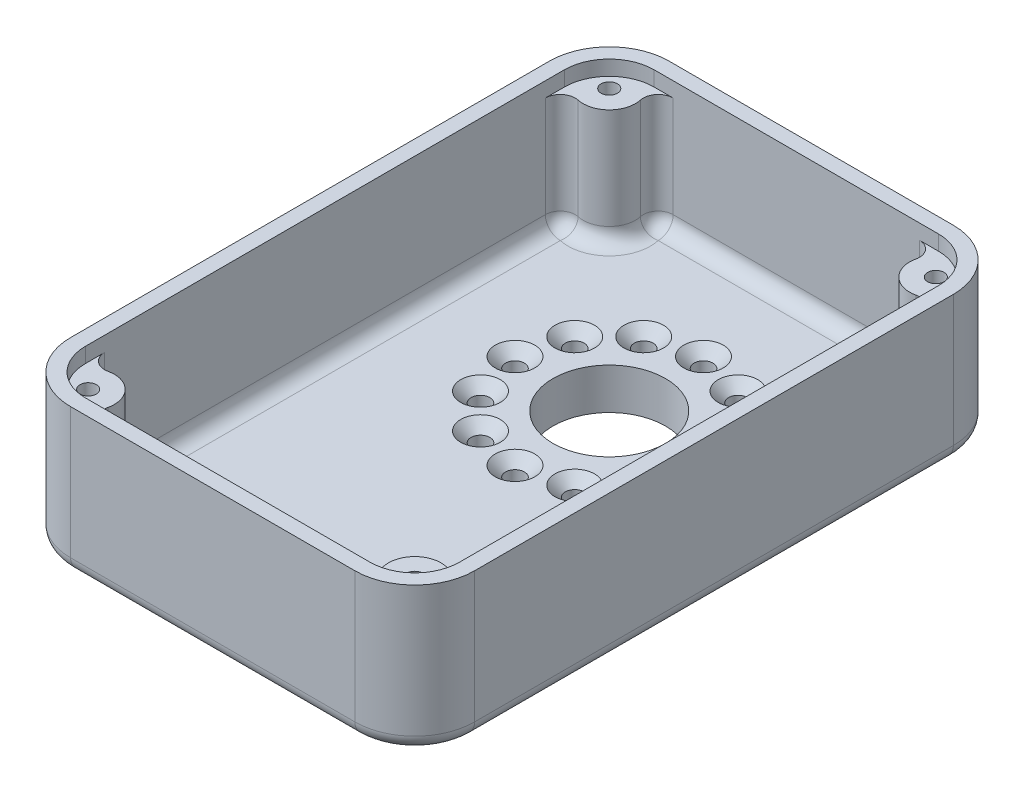
SolidWorks part; units mm, degrees
ref_plane "Front Plane" through (0, 0, 0) normal (0, 0, 1) x (1, 0, 0)
ref_plane "Top Plane" through (0, 0, 0) normal (0, 1, 0) x (1, 0, 0)
ref_plane "Right Plane" through (0, 0, 0) normal (1, 0, 0) x (0, 0, -1)
sketch "Sketch1" plane through (0, 0, 0) normal (0, 0, 1) x (1, 0, 0)
  line L0 (0, 0) -> (0, 10.3527) construction
  line L1 (-9.5504, 0) -> (-20.574, 0)
  line L2 (-20.574, 0) -> (-20.574, -5.08)
  line L3 (-20.574, -5.08) -> (-13.208, -5.08)
  line L4 (-13.208, -5.08) -> (-13.208, -4.445)
  line L5 (-13.208, -4.445) -> (-9.5504, -4.445)
  line L6 (-9.5504, -4.445) -> (-9.5504, 0)
  dimension "D1" = 20.574
  dimension "D2" = 9.5504
  dimension "D3" = 13.208
  dimension "D4" = 5.08
  dimension "D5" = 0.635
revolve "Revolve1" add sketch "Sketch1" angle 360 about L0
sketch "Sketch4" plane through (0, 0, 0) normal (0, 1, 0) x (1, 0, 0)
  line L0 (0, 0) -> (0, -36.4153) construction
  line L1 (-34.29, -16.51) -> (34.29, -16.51) construction
  line L2 (24.13, -67.31) -> (-24.13, -67.31)
  line L3 (34.29, -57.15) -> (34.29, 24.13)
  line L4 (24.13, 34.29) -> (-24.13, 34.29)
  line L5 (-34.29, -57.15) -> (-34.29, 24.13)
  line L6 (34.29, -67.31) -> (-34.29, 34.29) construction
  line L7 (34.29, 34.29) -> (-34.29, -67.31) construction
  line L8 (-24.13, -57.15) -> (0, -33.02) construction
  circle A0 centre (0, 0) radius 20.574 construction
  circle A1 centre (0, 0) radius 9.5504
  circle A2 centre (0, 0) radius 28.2956 construction
  circle A3 centre (0, 0) radius 30.8356 construction
  arc A4 (-34.29, -57.15) -> (-24.13, -67.31) centre (-24.13, -57.15) ccw
  arc A5 (24.13, -67.31) -> (34.29, -57.15) centre (24.13, -57.15) ccw
  arc A6 (34.29, 24.13) -> (24.13, 34.29) centre (24.13, 24.13) ccw
  arc A7 (-24.13, 34.29) -> (-34.29, 24.13) centre (-24.13, 24.13) ccw
  point P3 (0, -16.51)
  dimension "D3" = 34.29
  dimension "D4" = 2.54
  dimension "D5" = 10.16
  dimension "D1" = 68.58
  dimension "D2" = 101.6
  dimension "D6" = 135
extrude "Boss-Extrude1" add sketch "Sketch4" along normal blind 2.54
hole_wizard "CSK for M3 SFHCS1" positions "Sketch3" profile "Sketch2" countersink size "M3" standard "ANSI Metric" end condition through all
sketch "Sketch3" plane through (0, 2.54, 0) normal (0, 1, 0) x (1, 0, 0)
  line L0 (0, 0) -> (0, 1.3105) construction
  line L2 (0, 0) -> (-5.7425, 0) construction
  circle A0 centre (0, 0) radius 16.002 construction
  point P6 (-16.002, 0)
  point P15 (-13.8581, 8.001)
  point P16 (-8.001, 13.8581)
  point P34 (0, 16.002)
  point P35 (8.001, 13.8581)
  point P36 (13.8581, 8.001)
  point P37 (16.002, 0)
  point P38 (13.8581, -8.001)
  point P39 (8.001, -13.8581)
  point P40 (0, -16.002)
  point P41 (-8.001, -13.8581)
  point P42 (-13.8581, -8.001)
  dimension "D1" = 32.004
  dimension "D2" = 12
sketch "Sketch2" plane through (-13.8581, 2.54, 8.001) normal (1, 0, 0) x (0, 0, 1)
  line L0 (0, 0) -> (0, 7.62)
  line L1 (0, 7.62) -> (1.6, 7.62)
  line L2 (1.6, 7.62) -> (1.6, 1.76)
  line L3 (1.6, 1.76) -> (3.36, 0)
  line L5 (3.36, 0) -> (0, 0)
  line L6 (-1.6, 1.76) -> (-3.36, 0) construction
  line L11 (0, -6.35) -> (0, 107.95) construction
  dimension "Thru Hole Dia." = 3.2
  dimension "Thru Hole Depth" = 7.62
  dimension "Near C'Sink Dia." = 6.72
  dimension "Near C'Sink Angle" = 90
sketch "Sketch6" plane through (0, 2.54, 0) normal (0, 1, 0) x (1, 0, 0)
  line L6 (24.13, 34.29) -> (-24.13, 34.29)
  line L7 (-34.29, 24.13) -> (-34.29, -57.15)
  line L8 (-24.13, -67.31) -> (24.13, -67.31)
  line L9 (34.29, -57.15) -> (34.29, 24.13)
  line L10 (24.13, 31.75) -> (-24.13, 31.75)
  line L19 (31.75, -57.15) -> (31.75, 24.13)
  line L20 (-24.13, -64.77) -> (24.13, -64.77)
  line L21 (-31.75, 24.13) -> (-31.75, -57.15)
  line L22 (24.13, 31.75) -> (-24.13, 31.75)
  line L23 (31.75, -57.15) -> (31.75, 24.13)
  line L24 (-24.13, -64.77) -> (24.13, -64.77)
  line L25 (-31.75, 24.13) -> (-31.75, -57.15)
  arc A5 (-24.13, 34.29) -> (-34.29, 24.13) centre (-24.13, 24.13) ccw
  arc A6 (-34.29, -57.15) -> (-24.13, -67.31) centre (-24.13, -57.15) ccw
  arc A14 (24.13, -67.31) -> (34.29, -57.15) centre (24.13, -57.15) ccw
  arc A15 (34.29, 24.13) -> (24.13, 34.29) centre (24.13, 24.13) ccw
  arc A16 (31.75, 24.13) -> (24.13, 31.75) centre (24.13, 24.13) ccw
  arc A17 (-24.13, 31.75) -> (-31.75, 24.13) centre (-24.13, 24.13) ccw
  arc A18 (24.13, -64.77) -> (31.75, -57.15) centre (24.13, -57.15) ccw
  arc A19 (-31.75, -57.15) -> (-24.13, -64.77) centre (-24.13, -57.15) ccw
  arc A20 (31.75, 24.13) -> (24.13, 31.75) centre (24.13, 24.13) ccw
  arc A21 (-24.13, 31.75) -> (-31.75, 24.13) centre (-24.13, 24.13) ccw
  arc A22 (24.13, -64.77) -> (31.75, -57.15) centre (24.13, -57.15) ccw
  arc A23 (-31.75, -57.15) -> (-24.13, -64.77) centre (-24.13, -57.15) ccw
  dimension "D1" = 2.54
  dimension "D2" = 2.54
extrude "Boss-Extrude4" add sketch "Sketch6" along normal blind 22.225
fillet "Fillet1" radius 2.54 8 edges at (-31.3142, 0, 64.3342) (-34.29, 0, 16.51) (-31.3142, 0, -31.3142) (0, 0, -34.29) (31.3142, 0, -31.3142) (34.29, 0, 16.51) (31.3142, 0, 64.3342) (0, 0, 67.31)
sketch "Sketch8" plane through (0, 2.54, 0) normal (0, 1, 0) x (1, 0, 0)
  line L0 (-24.13, -57.15) -> (-46.8517, -79.8717) construction
  line L1 (-34.29, 24.13) -> (-34.29, -57.15) construction
  line L2 (0, -64.77) -> (0, 31.75) construction
  line L3 (-24.13, -64.77) -> (24.13, -64.77) construction
  line L4 (24.13, 31.75) -> (-24.13, 31.75) construction
  line L5 (0, -16.51) -> (-37.3684, -16.51) construction
  circle A0 centre (-27.7221, -60.7421) radius 4.445
  circle A1 centre (-27.7221, -60.7421) radius 1.3891
  circle A3 centre (27.7221, -60.7421) radius 1.3891
  circle A5 centre (27.7221, -60.7421) radius 4.445
  circle A6 centre (27.7221, 27.7221) radius 1.3891
  circle A7 centre (27.7221, 27.7221) radius 4.445
  circle A8 centre (-27.7221, 27.7221) radius 1.3891
  circle A9 centre (-27.7221, 27.7221) radius 4.445
  dimension "D2" = 2.7781
  dimension "D3" = 8.89
  dimension "D1" = 45
  dimension "D4" = 5.08
extrude "Boss-Extrude5" add sketch "Sketch8" along normal offset from surface (19.685 mm away) 2.54 up to face at (0, 24.765, 16.51)
fillet "Fillet3" radius 2.54 8 edges at (25.5718, 12.3825, 64.6324) (31.6124, 12.3825, 58.5918) (25.5718, 12.3825, -31.6124) (31.6124, 12.3825, -25.5718) (-31.6124, 12.3825, -25.5718) (-25.5718, 12.3825, -31.6124) (-31.6124, 12.3825, 58.5918) (-25.5718, 12.3825, 64.6324)
fillet "Fillet4" radius 2.54 16 edges at (-30.8033, 2.54, -22.8755) (-24.579, 2.54, -24.579) (-22.8755, 2.54, -30.8033) (0, 2.54, -31.75) (22.8755, 2.54, -30.8033) (24.579, 2.54, -24.579) (30.8033, 2.54, -22.8755) (31.75, 2.54, 16.51) (30.8033, 2.54, 55.8955) (24.579, 2.54, 57.599) (22.8755, 2.54, 63.8233) (0, 2.54, 64.77) (-22.8755, 2.54, 63.8233) (-24.579, 2.54, 57.599) (-30.8033, 2.54, 55.8955) (-31.75, 2.54, 16.51)
